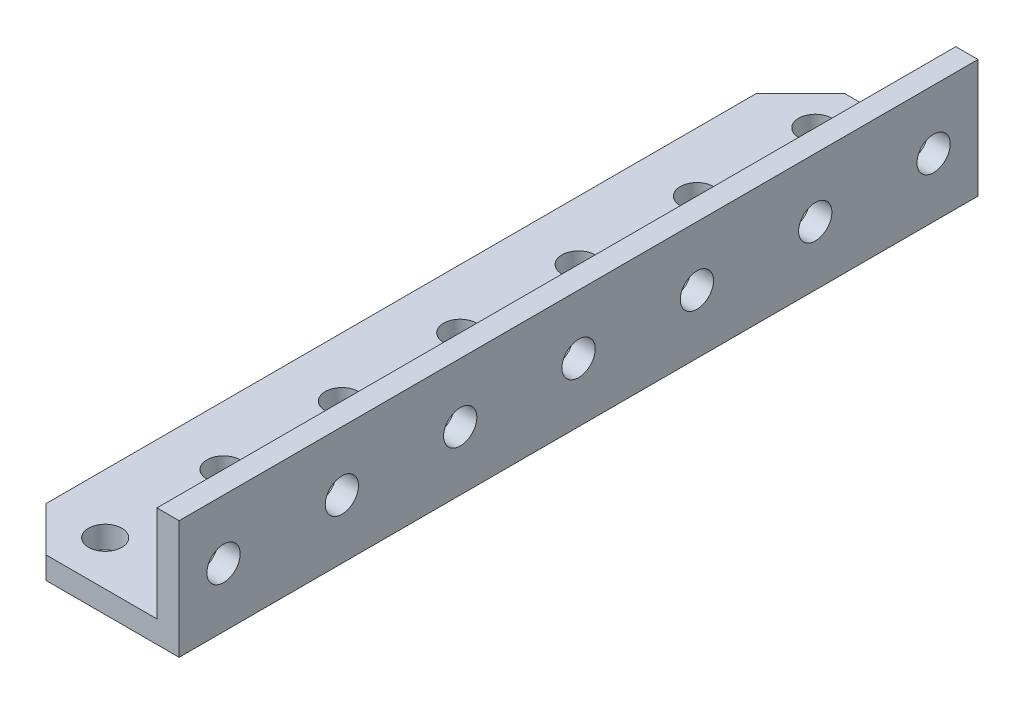
SolidWorks part; units mm, degrees
material "AISI Type 316L stainless steel"
ref_plane "Front Plane" through (0, 0, 0) normal (0, 0, 1) x (1, 0, 0)
ref_plane "Top Plane" through (0, 0, 0) normal (0, 1, 0) x (1, 0, 0)
ref_plane "Right Plane" through (0, 0, 0) normal (1, 0, 0) x (0, 0, -1)
sketch "Sketch1" plane through (0, 0, 0) normal (0, 0, 1) x (1, 0, 0)
  line L0 (0, 0) -> (38.1, 0)
  line L1 (38.1, 0) -> (38.1, 25.4)
  line L2 (38.1, 25.4) -> (33.3375, 25.4)
  line L3 (33.3375, 25.4) -> (33.3375, 4.7625)
  line L4 (33.3375, 4.7625) -> (0, 4.7625)
  line L5 (0, 4.7625) -> (0, 0)
  dimension "D1" = 38.1
  dimension "D2" = 25.4
  dimension "D3" = 4.7625
extrude "Boss-Extrude1" add sketch "Sketch1" along normal blind 177.8 contours L4 L5 L0 L1 L2 L3
sketch "Sketch6" plane through (0, 4.7625, 0) normal (0, 1, 0) x (1, 0, 0)
  line L0 (12.7, -177.8) -> (12.7, 0) construction
  line L1 (33.3375, -177.8) -> (0, -177.8) construction
  line L2 (33.3375, 0) -> (0, 0) construction
  line L6 (12.7, -165.1) -> (12.7, -139.7) construction
  line L7 (0, -177.8) -> (0, 0) construction
  point P8 (12.7, -165.1)
  point P38 (12.7, -139.7)
  point P39 (12.7, -114.3)
  point P40 (12.7, -88.9)
  point P41 (12.7, -63.5)
  point P42 (12.7, -38.1)
  point P43 (12.7, -12.7)
  dimension "D1" = 12.7
  dimension "D2" = 12.7
  dimension "D4" = 25.4
  dimension "D3" = 7
hole_wizard "1/4 Clearance Hole1" positions "Sketch6" profile "Sketch7" hole size "1/4" standard "ANSI Inch" end condition up to next
sketch "Sketch7" plane through (12.7, 4.7625, 12.7) normal (1, 0, 0) x (0, 0, 1)
  line L0 (0, 0) -> (0, 4.7625)
  line L1 (0, 4.7625) -> (3.5712, 4.7625)
  line L2 (3.5712, 4.7625) -> (3.5712, 0)
  line L5 (3.5712, 0) -> (0, 0)
  line L11 (0, -6.35) -> (0, 107.95) construction
  dimension "Thru Hole Dia." = 7.1425
  dimension "Thru Hole Depth" = 4.7625
sketch "Sketch8" plane through (33.3375, 0, 0) normal (-1, 0, 0) x (0, 0, 1)
  line L0 (0, 12.7) -> (177.8, 12.7) construction
  line L1 (0, 25.4) -> (0, 4.7625) construction
  line L4 (12.7, 12.7) -> (38.1, 12.7) construction
  line L6 (177.8, 25.4) -> (0, 25.4) construction
  line L7 (177.8, 25.4) -> (177.8, 4.7625) construction
  point P6 (12.7, 12.7)
  point P26 (38.1, 12.7)
  point P27 (63.5, 12.7)
  point P28 (88.9, 12.7)
  point P29 (114.3, 12.7)
  point P30 (139.7, 12.7)
  point P31 (165.1, 12.7)
  point P32 (190.5, 12.7)
  point P39 (0, 0)
  point P40 (0, 0)
  dimension "D1" = 12.7
  dimension "D3" = 25.4
  dimension "D4" = 12.7
  dimension "D2" = 8
hole_wizard "1/4 Clearance Hole2" positions "Sketch8" profile "Sketch9" hole size "1/4" standard "ANSI Inch" end condition up to next
sketch "Sketch9" plane through (33.3375, 12.7, 190.5) normal (0, 1, 0) x (0, 0, 1)
  line L0 (0, 0) -> (0, 4.7625)
  line L1 (0, 4.7625) -> (3.5712, 4.7625)
  line L2 (3.5712, 4.7625) -> (3.5712, 0)
  line L5 (3.5712, 0) -> (0, 0)
  line L11 (0, -6.35) -> (0, 107.95) construction
  dimension "Thru Hole Dia." = 7.1425
  dimension "Thru Hole Depth" = 4.7625
chamfer "Chamfer1" distance 12.7 angle 45 2 edges at (0, 2.3813, 177.8) (0, 2.3813, 0)
ref_plane "Plane1" through (0, 0, 88.9) normal (0, 0, -1) x (-1, 0, 0)
sketch "Sketch10" plane through (0, 0, 0) normal (0, 0, -1) x (-1, 0, 0)
  line L1 (-38.1, 25.4) -> (0, 25.4)
  line L2 (-38.1, 25.4) -> (-38.1, 0)
  line L3 (-38.1, 0) -> (0, 0)
  line L4 (0, 25.4) -> (0, 0)
extrude "Cut-Extrude1" cut sketch "Sketch10" against normal blind 3.175
mirror "Mirror1" about plane through (0, 0, 88.9) normal (0, 0, -1) of "Cut-Extrude1"
